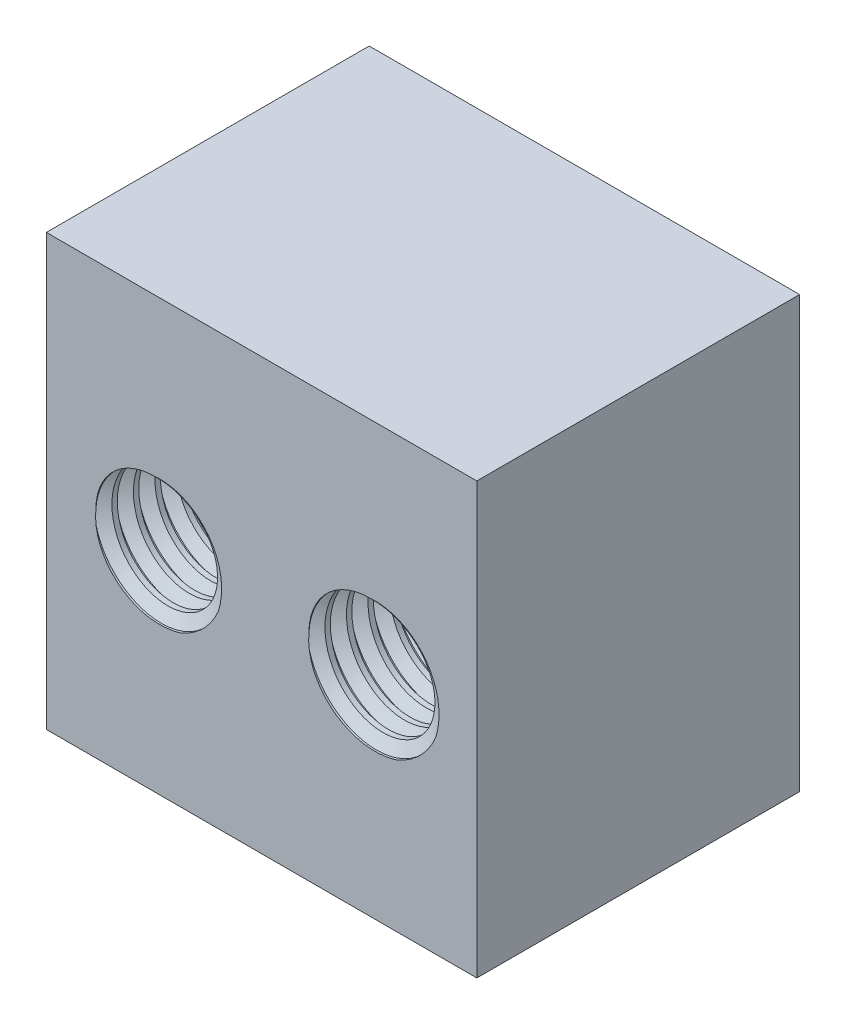
SolidWorks part; units mm, degrees
ref_plane "Front Plane" through (0, 0, 0) normal (0, 0, 1) x (1, 0, 0)
ref_plane "Top Plane" through (0, 0, 0) normal (0, 1, 0) x (1, 0, 0)
ref_plane "Right Plane" through (0, 0, 0) normal (1, 0, 0) x (0, 0, -1)
sketch "Sketch1" plane through (0, 0, 0) normal (0, 0, 1) x (1, 0, 0)
  line L1 (10, 10) -> (-10, 10)
  line L2 (10, 10) -> (10, -10)
  line L3 (10, -10) -> (-10, -10)
  line L4 (-10, 10) -> (-10, -10)
  line L5 (10, 10) -> (-10, -10) construction
  line L6 (10, -10) -> (-10, 10) construction
  point P0 (0, 0)
  dimension "D1" = 20
  dimension "D2" = 20
extrude "Boss-Extrude1" add sketch "Sketch1" along normal blind 15
sketch "Sketch2" plane through (0, 0, 15) normal (0, 0, 1) x (1, 0, 0)
  line L1 (-10, 10) -> (-10, -10) construction
  line L2 (10, -10) -> (10, 10) construction
  circle A1 centre (-5, 0) radius 2.7
  circle A2 centre (5, 0) radius 2.8
  dimension "D1" = 5.4
  dimension "D3" = 5.6
  dimension "D2" = 5
  dimension "D4" = 5
extrude "Cut-Extrude1" cut sketch "Sketch2" against normal blind 12
ref_plane "Plane2" through (0, 0, 17) normal (0, 0, 1) x (1, 0, 0)
thread "Thread2" pitch 1 method cut profile "Thread Profile4" start angle 0, offset 0, length 10, pitch 1, diameter 5.4
ref_plane "Plane5" through (-7.7, 0, 17) normal (0, -1, 0) x (-1, 0, 0)
sketch "Thread Profile4" plane through (-7.7, 0, 17) normal (0, -1, 0) x (-1, 0, 0)
  line L0 (0, 0) -> (0, 1) construction
  line L1 (0, 0) -> (0.5413, 0.3125)
  line L2 (0.5413, 0.3125) -> (0.5413, 0.4375)
  line L3 (0.5413, 0.4375) -> (0, 0.75)
  line L4 (0.5413, 0.375) -> (0, 0.375) construction
  line L11 (0, 0) -> (0, 0.75)
  point P2 (0, 0)
  dimension "Pitch" = 1
  dimension "Profile_Angle" = 60
  dimension "Profile_Land" = 0.125
  dimension "Profile_Height" = 0.5413
thread "Thread3" pitch 1 method cut profile "Thread Profile5" start angle 0, offset 0, length 10, pitch 1, diameter 5.6
ref_plane "Plane6" through (2.2, 0, 17) normal (0, -1, 0) x (-1, 0, 0)
sketch "Thread Profile5" plane through (2.2, 0, 17) normal (0, -1, 0) x (-1, 0, 0)
  line L0 (0, 0) -> (0, 1) construction
  line L1 (0, 0) -> (0.5413, 0.3125)
  line L2 (0.5413, 0.3125) -> (0.5413, 0.4375)
  line L3 (0.5413, 0.4375) -> (0, 0.75)
  line L4 (0.5413, 0.375) -> (0, 0.375) construction
  line L11 (0, 0) -> (0, 0.75)
  point P2 (0, 0)
  dimension "Pitch" = 1
  dimension "Profile_Angle" = 60
  dimension "Profile_Land" = 0.125
  dimension "Profile_Height" = 0.5413
